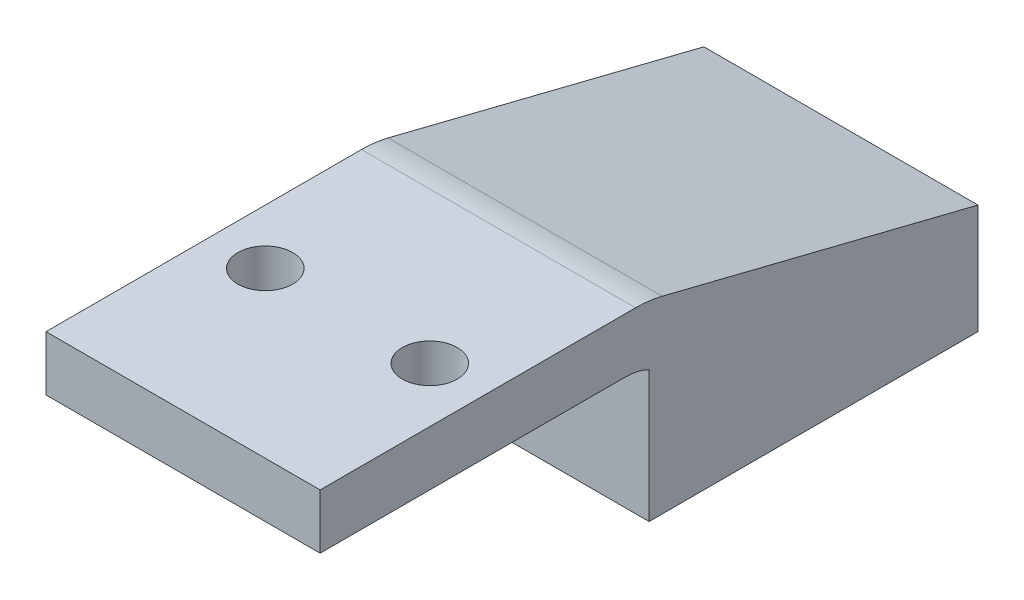
SolidWorks part; units mm, degrees
ref_plane "Front Plane" through (0, 0, 0) normal (0, 0, 1) x (1, 0, 0)
ref_plane "Top Plane" through (0, 0, 0) normal (0, 1, 0) x (1, 0, 0)
ref_plane "Right Plane" through (0, 0, 0) normal (1, 0, 0) x (0, 0, -1)
sketch "Sketch1" plane through (0, 0, 0) normal (1, 0, 0) x (0, 0, -1)
  line L0 (-30, 10) -> (-30, 25)
  line L1 (-30, 10) -> (30, 10)
  line L2 (-30, 10) -> (-30, -10)
  line L3 (-30, -10) -> (30, -10)
  line L4 (30, 10) -> (30, -10)
  line L5 (-30, 10) -> (30, -10) construction
  line L6 (-30, -10) -> (30, 10) construction
  line L7 (-30, 25) -> (30, 10)
  line L8 (-30, 25) -> (-90, 25)
  line L9 (-90, 25) -> (-90, 15)
  line L10 (-90, 15) -> (-30, 15)
  point P0 (0, 0)
  dimension "D1" = 60
  dimension "D2" = 20
  dimension "D3" = 15
  dimension "D4" = 60
  dimension "D5" = 10
extrude "Boss-Extrude1" add sketch "Sketch1" along normal blind 50 contours L4 L1 L2 L3 | L7 L0 L1 | L9 L10 L0 L8 region at (0, 15, 10) region at (0, 0, 0) region at (0, 20, 60)
fillet "Fillet1" radius 20 1 edges at (25, 25, 30)
sketch "Sketch2" plane through (0, 0, 0) normal (-1, 0, 0) x (0, 0, 1)
  line L0 (30, 15) -> (30, 14)
  line L1 (30, 15) -> (30, -10) construction
  line L2 (30, 14) -> (31, 15)
  line L3 (90, 15) -> (30, 15) construction
  line L4 (31, 15) -> (30, 15)
  dimension "D1" = 1
  dimension "D2" = 1
extrude "Boss-Extrude2" add sketch "Sketch2" against normal blind 50
fillet "Fillet2" radius 10 1 edges at (25, 15, 31)
sketch "Sketch3" plane through (0, 0, -30) normal (0, 0, -1) x (-1, 0, 0)
  line L0 (0, 10) -> (0, -10) construction
  line L1 (-50, -10) -> (0, -10) construction
  line L3 (-16.25, -15.1) -> (-16.75, -15.1)
  line L4 (-16.75, -15.1) -> (-16.75, -10)
  line L5 (-6.05, -15.1) -> (-5.55, -15.1)
  line L6 (-5.55, -15.1) -> (-5.55, -10)
  line L7 (-5.55, -10) -> (-16.75, -10)
  arc A0 (-6.05, -15.1) -> (-16.25, -15.1) centre (-11.15, -15.1) ccw
  point P0 (-11.15, -10)
  line M9 (-50, -10) -> (0, -10)
  dimension "D1" = 5.1
  dimension "D2" = 11.15
  dimension "D3" = 0.5
  dimension "D4" = 0.5
  dimension "D5" = 11.2
extrude "Boss-Extrude3" add sketch "Sketch3" against normal blind 20 contours A0 L5 L6 L7 | A0 L4 L3 M9 region at (6.7536, -11.5816, -30) region at (15.5464, -11.5816, -30)
fillet "Fillet3" radius 5 2 edges at (5.55, -10, -20) (16.75, -10, -20)
sketch "Sketch4" plane through (0, 25, 0) normal (0, 1, 0) x (1, 0, 0)
  line L0 (50, -90) -> (0, -90) construction
  line L2 (0, -32.4621) -> (0, -90) construction
  line L3 (50, -32.4621) -> (50, -90) construction
  line L4 (40, -60) -> (45, -60)
  circle A0 centre (10, -60) radius 5
  circle A1 centre (40, -60) radius 5
  dimension "D4" = 10
  dimension "D5" = 10
  dimension "D1" = 30
  dimension "D2" = 30
  dimension "D3" = 10
  dimension "D6" = 10
extrude "Cut-Extrude1" cut sketch "Sketch4" against normal blind 10 contours A0 | A1 region at (10, 25, 60) region at (35.1414, 25, 60)
